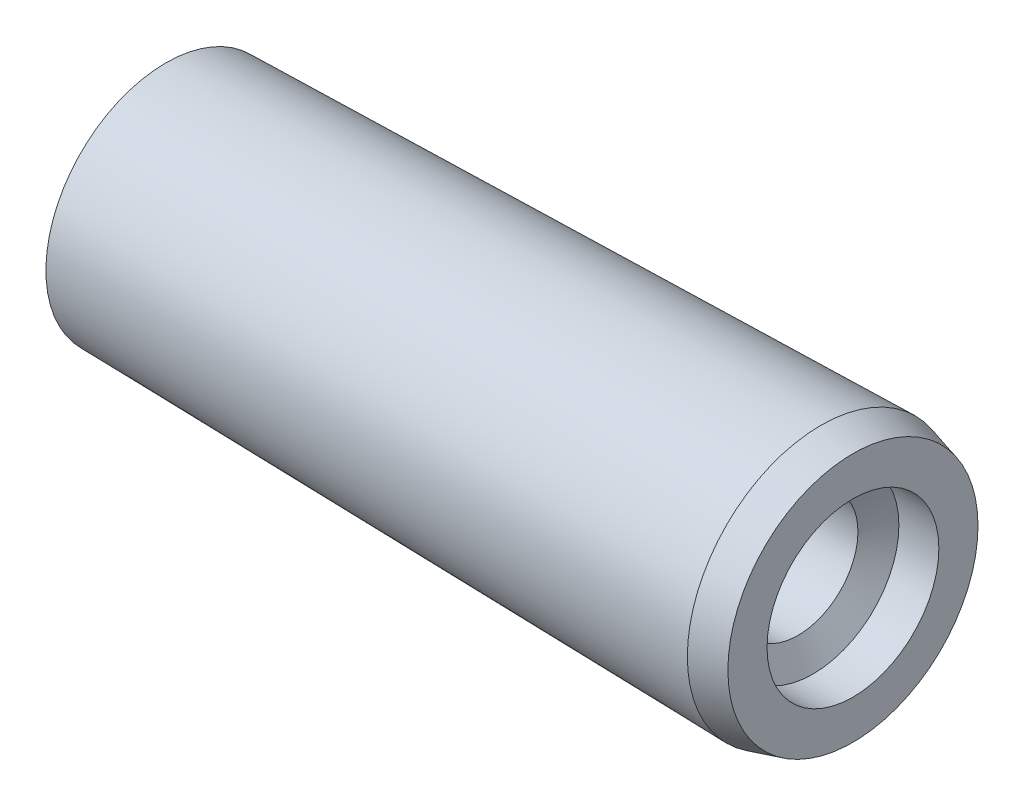
SolidWorks part; units mm, degrees
ref_plane "Front" through (0, 0, 0) normal (0, 0, 1) x (1, 0, 0)
ref_plane "Top" through (0, 0, 0) normal (0, 1, 0) x (1, 0, 0)
ref_plane "Right" through (0, 0, 0) normal (1, 0, 0) x (0, 0, -1)
sketch "Sketch1" plane through (0, 0, 0) normal (0, 0, 1) x (1, 0, 0)
  line L0 (0.8038, 0) -> (0.8038, 3) construction
  line L1 (0, 0) -> (18, 0) construction
  line L2 (18, 0) -> (18, 3.1296)
  line L3 (18, 3.1296) -> (17.2, 3.344)
  line L4 (17.2, 3.344) -> (0.8038, 3)
  line L5 (0.8038, 3) -> (17.2, 3) construction
  line L6 (18, 0) -> (16.0998, 0) construction
  line L7 (18, 0) -> (0, 0)
  line L8 (0, 0) -> (0, -2.2751) construction
  line L9 (17.2, 3) -> (17.2, 3.344) construction
  arc A0 (0.8038, 3) -> (0, 0) centre (6, 0) ccw
  dimension "D1" = 6
  dimension "D5" = 75
  dimension "D2" = 0.344
revolve "Body" add sketch "Sketch1" angle 360 about L7
sketch "Sketch2" plane through (0, 0, 0) normal (0, 0, 1) x (1, 0, 0)
  line L0 (18, 0) -> (18, 2.15)
  line L2 (18, 2.15) -> (17, 2.15)
  line L3 (17, 2.15) -> (16.6247, 1.5)
  line L4 (16.6247, 1.5) -> (8, 1.5)
  line L5 (8, 1.5) -> (7.134, 0)
  line L6 (7.134, 0) -> (18, 0)
  line L8 (18, 0) -> (13.9526, 0) construction
  line L9 (18, -3.1296) -> (18, 3.1296) construction
  dimension "d1" = 4.3
  dimension "D4" = 60
revolve "Hole" cut sketch "Sketch2" angle 360 about L8
cosmetic thread "ThreadCosmetic1" [suppressed] parameters "t1"=6, "d1"=4
sketch "Sketch3" plane through (0, 0, 0) normal (0, 0, 1) x (1, 0, 0)
  line L0 (16.0474, 1.5) -> (16.336, 2)
  line L1 (16.336, 2) -> (16.6247, 1.5)
  line L2 (16.6247, 1.5) -> (16.6247, 0.9226)
  line L3 (16.6247, 0.9226) -> (16.0474, 0.9226)
  line L4 (16.0474, 0.9226) -> (16.0474, 1.5)
  line L5 (0, 0) -> (23.9263, 0) construction
  line L6 (16.6247, 1.5) -> (8, 1.5) construction
  dimension "D1" = 4
revolve "Cut-Revolve10" [suppressed] cut sketch "Sketch3" angle 360 about L5
pattern_linear "LPattern10" [suppressed] count 8 spacing 0.75 along (-1, 0, 0) of bodies 103
equation "\"D1@Sketch1\" = \"d@Sketch1\""
equation "\"D2@Sketch1\" =  ( \"l@Sketch1\" - \"a@Sketch1\" )  / 50"
equation "\"D1@Sketch3\" = \"d1@ThreadCosmetic1\""
equation "\"D3@LPattern10\" = (  \"d1@ThreadCosmetic1\" - \"d0@Sketch2\" )  / 2 * 1.5"
equation "\"D1@LPattern10\" = \"t1@ThreadCosmetic1\" / \"D3@LPattern10\""
